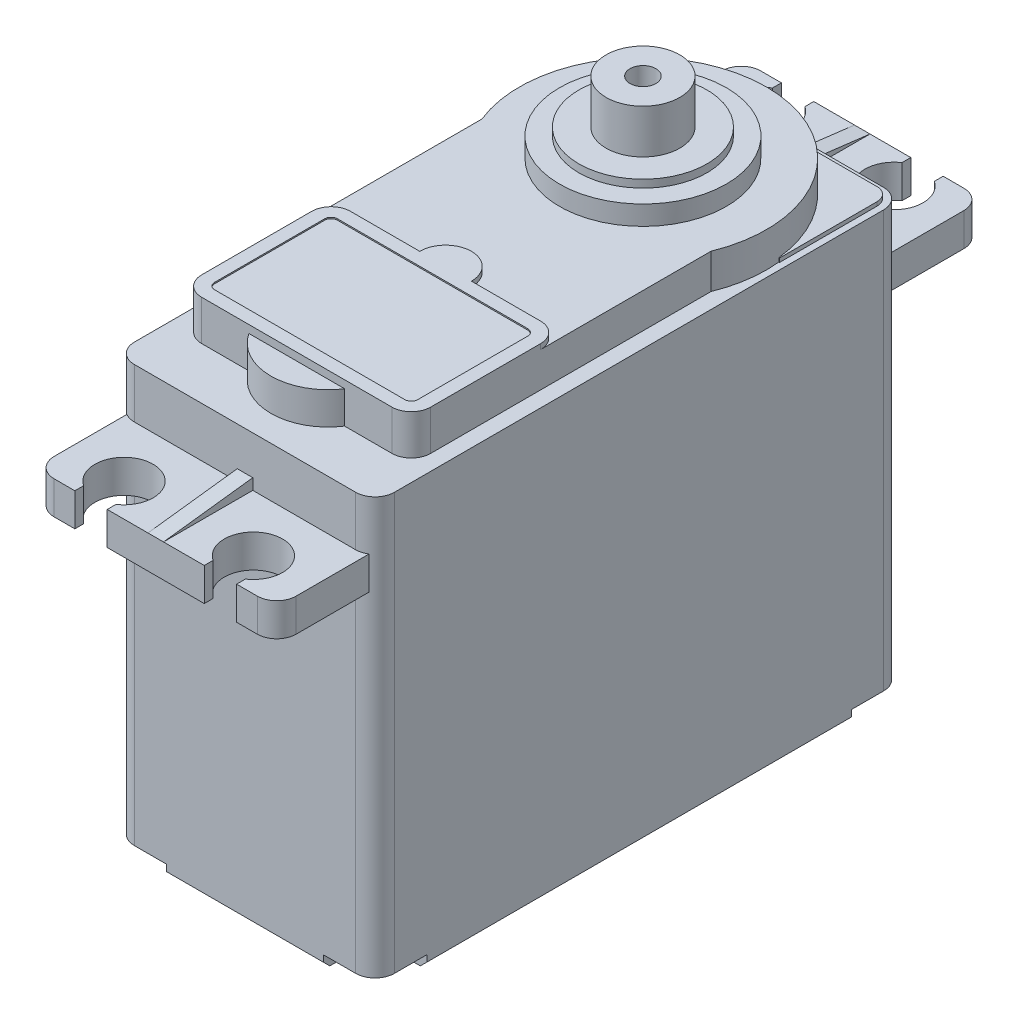
SolidWorks part; units mm, degrees
material "Feetech servo "
ref_plane "Front Plane" through (0, 0, 0) normal (0, 0, 1) x (1, 0, 0)
ref_plane "Top Plane" through (0, 0, 0) normal (0, 1, 0) x (1, 0, 0)
ref_plane "Right Plane" through (0, 0, 0) normal (1, 0, 0) x (0, 0, -1)
sketch "Sketch1" plane through (0, 0, 0) normal (0, 1, 0) x (1, 0, 0)
  line L0 (-10.05, -5.18) -> (10.05, -5.18) construction
  line L1 (-8.55, -25.58) -> (8.55, -25.58)
  line L2 (-10.05, -24.08) -> (-10.05, 13.72)
  line L3 (-8.55, 15.22) -> (8.55, 15.22)
  line L4 (10.05, -24.08) -> (10.05, 13.72)
  line L5 (-10.05, -25.58) -> (10.05, 15.22) construction
  line L6 (-10.05, 15.22) -> (10.05, -25.58) construction
  line L7 (0, -5.18) -> (0, 15.22) construction
  arc A0 (-10.05, 13.72) -> (-8.55, 15.22) centre (-8.55, 13.72) cw
  arc A1 (8.55, 15.22) -> (10.05, 13.72) centre (8.55, 13.72) cw
  arc A2 (10.05, -24.08) -> (8.55, -25.58) centre (8.55, -24.08) cw
  arc A3 (-8.55, -25.58) -> (-10.05, -24.08) centre (-8.55, -24.08) cw
  point P0 (0, 0)
  dimension "D5" = 1.5
  dimension "D1" = 20.1
  dimension "D2" = 40.8
  dimension "D3" = 25.58
extrude "Boss-Extrude1" add sketch "Sketch1" along normal blind 33.2
ref_plane "Plane1" through (0, 26.8, 0) normal (0, 1, 0) x (1, 0, 0)
sketch "Sketch4" plane through (0, 26.8, 0) normal (0, 1, 0) x (1, 0, 0)
  line L0 (-6.25, 22.12) -> (-6.25, 21.4408)
  line L1 (-7.85, -32.48) -> (-6.25, -32.48)
  line L2 (-9.35, -30.98) -> (-9.35, 20.62)
  line L3 (-7.85, 22.12) -> (-6.25, 22.12)
  line L4 (9.35, -30.98) -> (9.35, 20.62)
  line L5 (-9.35, -32.48) -> (9.35, 22.12) construction
  line L6 (-9.35, 22.12) -> (9.35, -32.48) construction
  line L7 (-3.75, 22.12) -> (-3.75, 21.4408)
  line L8 (-3.75, 22.12) -> (3.75, 22.12)
  line L9 (-10.05, -5.18) -> (10.05, -5.18) construction
  line L10 (6.25, 22.12) -> (7.85, 22.12)
  line L11 (6.25, -32.48) -> (6.25, -31.8008)
  line L12 (3.75, -32.48) -> (3.75, -31.8008)
  line L13 (0, -25.58) -> (0, 15.22) construction
  line L14 (-8.55, -25.58) -> (8.55, -25.58) construction
  line L15 (8.55, 15.22) -> (-8.55, 15.22) construction
  line L16 (-3.75, -32.48) -> (3.75, -32.48)
  line L17 (3.75, 22.12) -> (3.75, 21.4408)
  line L18 (6.25, 22.12) -> (6.25, 21.4408)
  line L19 (-3.75, -32.48) -> (-3.75, -31.8008)
  line L20 (-6.25, -32.48) -> (-6.25, -31.8008)
  line L21 (6.25, -32.48) -> (7.85, -32.48)
  line L22 (-10.05, 13.72) -> (-10.05, -24.08) construction
  arc A0 (7.85, 22.12) -> (9.35, 20.62) centre (7.85, 20.62) cw
  arc A1 (9.35, -30.98) -> (7.85, -32.48) centre (7.85, -30.98) cw
  arc A2 (-7.85, -32.48) -> (-9.35, -30.98) centre (-7.85, -30.98) cw
  arc A3 (-9.35, 20.62) -> (-7.85, 22.12) centre (-7.85, 20.62) cw
  arc A4 (-6.25, 21.4408) -> (-3.75, 21.4408) centre (-5, 19.57) ccw
  arc A5 (6.25, -31.8008) -> (3.75, -31.8008) centre (5, -29.93) ccw
  arc A6 (6.25, 21.4408) -> (3.75, 21.4408) centre (5, 19.57) cw
  arc A7 (-6.25, -31.8008) -> (-3.75, -31.8008) centre (-5, -29.93) cw
  point P0 (0, -5.18)
  dimension "D3" = 1.5
  dimension "D4" = 2.5
  dimension "D5" = 2.25
  dimension "D1" = 18.7
  dimension "D6" = 0.6792
  dimension "D7" = 10
  dimension "D8" = 49.5
extrude "Boss-Extrude2" add sketch "Sketch4" along normal blind 2.55
sketch "Sketch16" plane through (0, 33.2, 0) normal (0, 1, 0) x (1, 0, 0)
  line L0 (-9.55, 6.17) -> (9.55, 6.17)
  line L1 (0, 14.72) -> (0, -2.38) construction
  line L8 (-9.55, 13.72) -> (-9.55, -24.08)
  line L9 (-8.55, -25.08) -> (8.55, -25.08)
  line L10 (9.55, -24.08) -> (9.55, 13.72)
  line L11 (8.55, 14.72) -> (-8.55, 14.72)
  line L12 (-9.55, 13.72) -> (-9.55, -24.08)
  line L13 (-8.55, -25.08) -> (8.55, -25.08)
  line L14 (9.55, -24.08) -> (9.55, 13.72)
  line L15 (8.55, 14.72) -> (-8.55, 14.72)
  arc A8 (-8.55, 14.72) -> (-9.55, 13.72) centre (-8.55, 13.72) ccw
  arc A9 (-9.55, -24.08) -> (-8.55, -25.08) centre (-8.55, -24.08) ccw
  arc A10 (8.55, -25.08) -> (9.55, -24.08) centre (8.55, -24.08) ccw
  arc A11 (9.55, 13.72) -> (8.55, 14.72) centre (8.55, 13.72) ccw
  arc A12 (-8.55, 14.72) -> (-9.55, 13.72) centre (-8.55, 13.72) ccw
  arc A13 (-9.55, -24.08) -> (-8.55, -25.08) centre (-8.55, -24.08) ccw
  arc A14 (8.55, -25.08) -> (9.55, -24.08) centre (8.55, -24.08) ccw
  arc A15 (9.55, 13.72) -> (8.55, 14.72) centre (8.55, 13.72) ccw
  point P4 (0, 6.17)
  dimension "D1" = 0.5
extrude "Boss-Extrude11" add sketch "Sketch16" along normal blind 0.3 contours L1 L15 A12 L12 L0 | L15 L1 L0 L14 A15 region at (-4.763, 33.2, -10.4343) region at (4.763, 33.2, -10.4343)
sketch "Sketch5" plane through (0, 33.2, 0) normal (0, 1, 0) x (1, 0, 0)
  line L0 (8.55, -25.58) -> (-8.55, -25.58) construction
  line L1 (9.55, 6.17) -> (9.55, 13.72) construction
  line L2 (-8.85, 1.5811) -> (-8.85, -20.08)
  line L3 (-7.35, -21.58) -> (7.35, -21.58)
  line L4 (8.85, 1.5811) -> (8.85, -20.08)
  line L5 (-9.55, 13.72) -> (-9.55, 6.17) construction
  line L6 (0, 5.17) -> (0, -21.58) construction
  line L7 (8.55, 14.72) -> (-8.55, 14.72) construction
  arc A0 (8.85, 1.5811) -> (-8.85, 1.5811) centre (0, 5.17) ccw
  arc A1 (8.85, -20.08) -> (7.35, -21.58) centre (7.35, -20.08) cw
  arc A2 (-7.35, -21.58) -> (-8.85, -20.08) centre (-7.35, -20.08) cw
  dimension "D2" = 1.5
  dimension "D3" = 17.7
  dimension "D6" = 4
extrude "Boss-Extrude3" add sketch "Sketch5" along normal blind 2.7
sketch "Sketch6" plane through (0, 33.2, 0) normal (0, 1, 0) x (1, 0, 0)
  circle A0 centre (0, -19.1575) radius 4.4225
extrude "Boss-Extrude4" add sketch "Sketch6" along normal blind 2.5
sketch "Sketch7" plane through (0, 35.9, 0) normal (0, 1, 0) x (1, 0, 0)
  circle A0 centre (0, 5.17) radius 6.45
  arc A1 (8.85, 1.5811) -> (-8.85, 1.5811) centre (0, 5.17) ccw construction
  dimension "D1" = 12.9
extrude "Boss-Extrude5" add sketch "Sketch7" along normal blind 1.5
sketch "Sketch8" plane through (0, 37.4, 0) normal (0, 1, 0) x (1, 0, 0)
  circle A2 centre (0, 5.17) radius 4.95
  circle A3 centre (0, 5.17) radius 4.95
  dimension "D1" = 1.5
extrude "Boss-Extrude6" add sketch "Sketch8" along normal blind 0.6
sketch "Sketch10" plane through (0, 38, 0) normal (0, 1, 0) x (1, 0, 0)
  circle A1 centre (0, 5.17) radius 2.85
  dimension "D1" = 5.7
extrude "Boss-Extrude7" add sketch "Sketch10" along normal blind 3.4
sketch "Sketch12" plane through (0, 41.4, 0) normal (0, 1, 0) x (1, 0, 0)
  circle A0 centre (0, 5.17) radius 1
  dimension "D1" = 2
extrude "Cut-Extrude1" cut sketch "Sketch12" against normal blind 5
sketch "Sketch13" plane through (0, 35.9, 0) normal (0, 1, 0) x (1, 0, 0)
  line L0 (-8.85, 1.5811) -> (-8.85, -20.08) construction
  line L1 (-7.35, -21.58) -> (7.35, -21.58) construction
  line L2 (8.85, -20.08) -> (8.85, 1.5811) construction
  line L3 (-8.85, -11.58) -> (-8.85, -20.08)
  line L4 (-7.35, -21.58) -> (7.35, -21.58)
  line L5 (8.85, -20.08) -> (8.85, -11.58)
  line L6 (-7.85, -11.58) -> (-7.85, -20.08)
  line L7 (-7.35, -20.58) -> (7.35, -20.58)
  line L8 (7.85, -20.08) -> (7.85, -11.58)
  line L9 (-7.35, -11.08) -> (7.35, -11.08)
  line L10 (-7.35, -10.08) -> (-2, -10.08)
  line L11 (2, -10.08) -> (7.35, -10.08)
  line L12 (0, -10.08) -> (0, -11.08) construction
  arc A0 (-8.85, -20.08) -> (-7.35, -21.58) centre (-7.35, -20.08) ccw construction
  arc A1 (7.35, -21.58) -> (8.85, -20.08) centre (7.35, -20.08) ccw construction
  arc A2 (-8.85, -20.08) -> (-7.35, -21.58) centre (-7.35, -20.08) ccw
  arc A3 (7.35, -21.58) -> (8.85, -20.08) centre (7.35, -20.08) ccw
  arc A4 (-7.85, -20.08) -> (-7.35, -20.58) centre (-7.35, -20.08) ccw
  arc A5 (7.35, -20.58) -> (7.85, -20.08) centre (7.35, -20.08) ccw
  arc A6 (7.35, -11.08) -> (7.85, -11.58) centre (7.35, -11.58) cw
  arc A7 (-7.35, -11.08) -> (-7.85, -11.58) centre (-7.35, -11.58) ccw
  arc A8 (7.35, -10.08) -> (8.85, -11.58) centre (7.35, -11.58) cw
  arc A9 (-7.35, -10.08) -> (-8.85, -11.58) centre (-7.35, -11.58) ccw
  arc A10 (2, -10.08) -> (-2, -10.08) centre (0, -10.08) ccw
  point P8 (-7.85, 0.3518)
  point P15 (7.85, 0.3518)
  dimension "D2" = 0.5
  dimension "D1" = 1
  dimension "D3" = 1.5
  dimension "D4" = 4
  dimension "D5" = 9.5
extrude "Boss-Extrude9" add sketch "Sketch13" along normal blind 0.4
sketch "Sketch14" plane through (0, 35.9, 0) normal (0, 1, 0) x (1, 0, 0)
  line L3 (-7.85, -11.58) -> (-7.85, -20.08)
  line L4 (-7.85, -11.58) -> (-7.85, -20.08)
  line L5 (-7.35, -20.58) -> (7.35, -20.58)
  line L6 (-7.35, -20.58) -> (7.35, -20.58)
  line L7 (7.85, -20.08) -> (7.85, -11.58)
  line L8 (7.85, -20.08) -> (7.85, -11.58)
  line L10 (7.35, -11.08) -> (-7.35, -11.08)
  line L11 (7.35, -11.08) -> (-7.35, -11.08)
  arc A3 (-7.85, -20.08) -> (-7.35, -20.58) centre (-7.35, -20.08) ccw
  arc A4 (-7.85, -20.08) -> (-7.35, -20.58) centre (-7.35, -20.08) ccw
  arc A5 (7.35, -20.58) -> (7.85, -20.08) centre (7.35, -20.08) ccw
  arc A6 (7.35, -20.58) -> (7.85, -20.08) centre (7.35, -20.08) ccw
  arc A7 (7.85, -11.58) -> (7.35, -11.08) centre (7.35, -11.58) ccw
  arc A8 (7.85, -11.58) -> (7.35, -11.08) centre (7.35, -11.58) ccw
  arc A10 (-7.35, -11.08) -> (-7.85, -11.58) centre (-7.35, -11.58) ccw
  arc A11 (-7.35, -11.08) -> (-7.85, -11.58) centre (-7.35, -11.58) ccw
  dimension "D1" = 0
extrude "Boss-Extrude10" add sketch "Sketch14" along normal blind 0.3
chamfer "Chamfer1" distance 0.5 angle 45 8 edges at (-10.05, 0, 5.18) (-9.6107, 0, 25.1407) (0, 0, 25.58) (9.6107, 0, 25.1407) (10.05, 0, 5.18) (9.6107, 0, -14.7807) (0, 0, -15.22) (-9.6107, 0, -14.7807)
sketch "Sketch17" plane through (0, 0, 0) normal (0, -1, 0) x (1, 0, 0)
  line L0 (-10.05, -13.72) -> (-10.05, 24.08) construction
  line L1 (-8.55, 25.58) -> (8.55, 25.58) construction
  line L3 (-10.05, 21.58) -> (-10.05, 24.08)
  line L4 (-8.55, 25.58) -> (-6.05, 25.58)
  line L5 (-6.05, 25.58) -> (-6.05, 23.08)
  line L6 (-7.55, 21.58) -> (-10.05, 21.58)
  arc A0 (-8.55, 25.58) -> (-10.05, 24.08) centre (-8.55, 24.08) ccw construction
  arc A3 (-8.55, 25.58) -> (-10.05, 24.08) centre (-8.55, 24.08) ccw
  arc A4 (-6.05, 23.08) -> (-7.55, 21.58) centre (-7.55, 23.08) cw
  point P10 (-6.05, 21.58)
  dimension "D3" = 1.5
  dimension "D1" = 4
  dimension "D2" = 4
extrude "Cut-Extrude2" cut sketch "Sketch17" against normal blind 1
mirror "Mirror1" about plane through (0, 0, 0) normal (1, 0, 0) of "Cut-Extrude2"
ref_plane "Plane2" through (0, 0, 5.18) normal (0, 0, 1) x (1, 0, 0)
mirror "Mirror2" about plane through (0, 0, 5.18) normal (0, 0, 1) of "Mirror1", "Cut-Extrude2"
sketch "Sketch19" plane through (0, 0, 0) normal (1, 0, 0) x (0, 0, -1)
  line L0 (-25.58, 30.2) -> (-25.58, 29.35)
  line L1 (-25.58, 33.2) -> (-25.58, 29.35) construction
  line L2 (-25.58, 29.35) -> (-32.48, 29.35)
  line L3 (-32.48, 29.35) -> (-25.58, 30.2)
  line L4 (15.22, 30.2) -> (15.22, 29.35)
  line L5 (15.22, 33.2) -> (15.22, 29.35) construction
  line L6 (14.9889, 29.35) -> (20.62, 29.35) construction
  line L7 (15.22, 29.35) -> (22.12, 29.35)
  line L8 (22.12, 29.35) -> (15.22, 30.2)
  dimension "D1" = 0.85
extrude "Boss-Extrude12" add sketch "Sketch19" along normal mid plane 1.2
